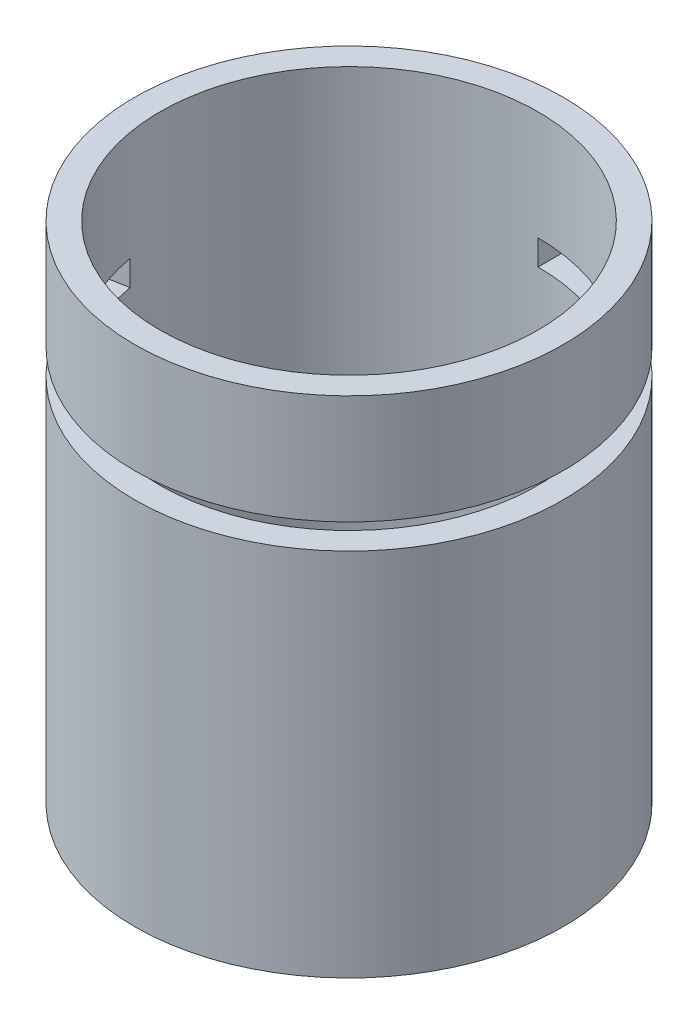
SolidWorks part; units mm, degrees
ref_plane "前视基准面" through (0, 0, 0) normal (0, 0, 1) x (1, 0, 0)
ref_plane "上视基准面" through (0, 0, 0) normal (0, 1, 0) x (1, 0, 0)
ref_plane "右视基准面" through (0, 0, 0) normal (1, 0, 0) x (0, 0, -1)
sketch "草图1" plane through (0, 0, 0) normal (0, 1, 0) x (1, 0, 0)
  circle A0 centre (0, 0) radius 22.5
  circle A1 centre (0, 0) radius 25.5
  dimension "D1" = 45
  dimension "D2" = 3
extrude "凸台-拉伸1" add sketch "草图1" along normal blind 60
sketch "草图2" plane through (0, 0, 0) normal (1, 0, 0) x (0, 0, -1)
  line L0 (0, 60.3381) -> (0, -18.3267) construction
  line L2 (0, 44) -> (46.8092, 44)
  line L3 (0, 44) -> (0, 47)
  line L4 (0, 47) -> (46.8092, 47)
  line L5 (46.8092, 44) -> (46.8092, 47)
  line L6 (-25.5, 0) -> (25.5, 0) construction
  dimension "D1" = 44
  dimension "D2" = 3
ref_axis "基准轴1" through (0, 64.2714, 0) along (0, -1, 0)
revolve "切除-旋转1" cut sketch "草图2" angle 260 about L0
